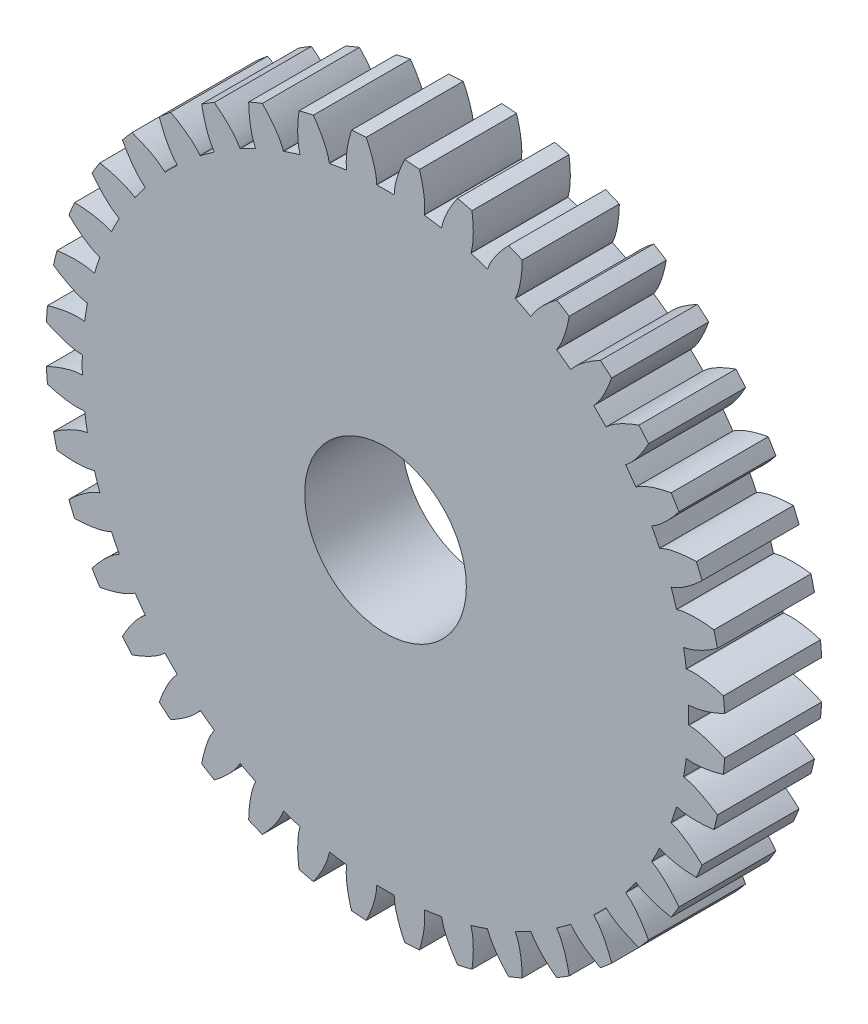
SolidWorks part; units mm, degrees
ref_plane "前视基准面" through (0, 0, 0) normal (0, 0, 1) x (1, 0, 0)
ref_plane "上视基准面" through (0, 0, 0) normal (0, 1, 0) x (1, 0, 0)
ref_plane "右视基准面" through (0, 0, 0) normal (1, 0, 0) x (0, 0, -1)
other "Configuration Table"
sketch "草图1" plane through (0, 0, 0) normal (0, 0, 1) x (1, 0, 0)
  line L0 (0, 0) -> (4, 0) construction
  line L1 (0, 0) -> (3.9969, 0.157) construction
  line L2 (0, 0) -> (3.7572, 0.1081)
  line L3 (3.9969, 0.157) -> (3.9969, -0.157) construction
  line L4 (0, 0) -> (3.7572, -0.1081)
  circle A0 centre (0, 0) radius 4.2
  circle A1 centre (0, 0) radius 4 construction
  circle A2 centre (0, 0) radius 3.75
  circle A3 centre (0, 0) radius 3.7588 construction
  circle A4 centre (0, 0) radius 1
  spline S0 degree 4 poles (3.7572, 0.1081) (3.7859, 0.1089) (3.8656, 0.1171) (4.0142, 0.1566) (4.244, 0.2529) (4.5194, 0.4228) (4.8383, 0.6887) (5.1613, 1.0532) (5.4549, 1.5001) (5.7635, 2.151) (5.9615, 2.8455) (6.0613, 3.5884) (6.0582, 4.4803) (5.9407, 5.366) (5.6554, 6.3645) (5.1709, 7.4112) (4.5413, 8.377) (3.7872, 9.2487) (2.9285, 10.0168) (1.983, 10.6749) (0.9682, 11.219) (0.0323, 11.5933) (-0.7245, 11.8205) (-1.2852, 11.952) (-1.6352, 12.022) (-1.9233, 12.071) (-2.1979, 12.1123) (-2.5004, 12.1475) (-2.7337, 12.1714) (-3.0025, 12.1902) (-3.2739, 12.2053) (-3.546, 12.2135) (-4.0234, 12.217) (-4.4129, 12.1964) (-4.8168, 12.1721) (-5.0123, 12.1473) (-5.1429, 12.1347) knots 0 0 0 0 0 0.005604 0.015718 0.02996 0.048734 0.068727 0.096889 0.125051 0.153212 0.209535 0.237696 0.271429 0.327752 0.384075 0.440398 0.496721 0.553044 0.609367 0.66569 0.722013 0.778336 0.806497 0.820578 0.834659 0.84874 0.86282 0.876901 0.890982 0.900036 0.909091 0.931818 0.954545 0.977273 1 1 1 1 1 construction
  spline S1 degree 4 poles (3.7572, 0.1081) (3.7859, 0.1089) (3.8656, 0.1171) (4.0142, 0.1566) (4.244, 0.2529) (4.5194, 0.4228) (4.8383, 0.6887) (5.1613, 1.0532) (5.4549, 1.5001) (5.7635, 2.151) (5.9615, 2.8455) (6.0613, 3.5884) (6.0582, 4.4803) (5.9407, 5.366) (5.6554, 6.3645) (5.1709, 7.4112) (4.5413, 8.377) (3.7872, 9.2487) (2.9285, 10.0168) (1.983, 10.6749) (0.9682, 11.219) (0.0323, 11.5933) (-0.7245, 11.8205) (-1.2852, 11.952) (-1.6352, 12.022) (-1.9233, 12.071) (-2.1979, 12.1123) (-2.5004, 12.1475) (-2.7337, 12.1714) (-3.0025, 12.1902) (-3.1616, 12.199) (-3.2457, 12.2029) (-3.2877, 12.2045) knots 0 0 0 0 0 0.005604 0.015718 0.02996 0.048734 0.068727 0.096889 0.125051 0.153212 0.209535 0.237696 0.271429 0.327752 0.384075 0.440398 0.496721 0.553044 0.609367 0.66569 0.722013 0.778336 0.806497 0.820578 0.834659 0.84874 0.86282 0.876901 0.890982 0.900036 0.909091 0.909091 0.909091 0.909091 0.909091
  spline S2 degree 4 poles (3.7572, -0.1081) (3.7859, -0.1089) (3.8656, -0.1171) (4.0142, -0.1566) (4.244, -0.2529) (4.5194, -0.4228) (4.8383, -0.6887) (5.1613, -1.0532) (5.4549, -1.5001) (5.7635, -2.151) (5.9615, -2.8455) (6.0613, -3.5884) (6.0582, -4.4803) (5.9407, -5.366) (5.6554, -6.3645) (5.1709, -7.4112) (4.5413, -8.377) (3.7872, -9.2487) (2.9285, -10.0168) (1.983, -10.6749) (0.9682, -11.219) (0.0323, -11.5933) (-0.7245, -11.8205) (-1.2852, -11.952) (-1.6352, -12.022) (-1.9233, -12.071) (-2.1979, -12.1123) (-2.5004, -12.1475) (-2.7337, -12.1714) (-3.0025, -12.1902) (-3.2739, -12.2053) (-3.546, -12.2135) (-4.0234, -12.217) (-4.4129, -12.1964) (-4.8168, -12.1721) (-5.0123, -12.1473) (-5.1429, -12.1347) knots 0 0 0 0 0 0.005604 0.015718 0.02996 0.048734 0.068727 0.096889 0.125051 0.153212 0.209535 0.237696 0.271429 0.327752 0.384075 0.440398 0.496721 0.553044 0.609367 0.66569 0.722013 0.778336 0.806497 0.820578 0.834659 0.84874 0.86282 0.876901 0.890982 0.900036 0.909091 0.931818 0.954545 0.977273 1 1 1 1 1 construction
  spline S3 degree 4 poles (3.7572, -0.1081) (3.7859, -0.1089) (3.8656, -0.1171) (4.0142, -0.1566) (4.244, -0.2529) (4.5194, -0.4228) (4.8383, -0.6887) (5.1613, -1.0532) (5.4549, -1.5001) (5.7635, -2.151) (5.9615, -2.8455) (6.0613, -3.5884) (6.0582, -4.4803) (5.9407, -5.366) (5.6554, -6.3645) (5.1709, -7.4112) (4.5413, -8.377) (3.7872, -9.2487) (2.9285, -10.0168) (1.983, -10.6749) (0.9682, -11.219) (0.0323, -11.5933) (-0.7245, -11.8205) (-1.2852, -11.952) (-1.6352, -12.022) (-1.9233, -12.071) (-2.1979, -12.1123) (-2.5004, -12.1475) (-2.7337, -12.1714) (-3.0025, -12.1902) (-3.1616, -12.199) (-3.2457, -12.2029) (-3.2877, -12.2045) knots 0 0 0 0 0 0.005604 0.015718 0.02996 0.048734 0.068727 0.096889 0.125051 0.153212 0.209535 0.237696 0.271429 0.327752 0.384075 0.440398 0.496721 0.553044 0.609367 0.66569 0.722013 0.778336 0.806497 0.820578 0.834659 0.84874 0.86282 0.876901 0.890982 0.900036 0.909091 0.909091 0.909091 0.909091 0.909091
  point P15 (3.9969, 0)
  dimension "齿顶圆直径" = 8.4
  dimension "分度圆直径" = 8
  dimension "齿根圆直径" = 7.5
  dimension "基圆直径" = 7.5175
  dimension "内孔直径" = 2
  dimension "渐近线镜像线夹角" = 2.25
extrude "凸台-拉伸1" add sketch "草图1" along normal blind 1.2 contours A0 | A4
extrude "切除-拉伸1" cut sketch "草图1<3>" along normal through all contours A2 S3 A0 S1 region at (4.0059, 0, 0)
sketch "草图1<3>" plane through (0, 0, 0) normal (0, 0, 1) x (1, 0, 0) same geometry as "草图1"
pattern_circular "阵列(圆周)1" count 40 every 9 about axis through (0, 0, 1.2) along (0, 0, 1) of "切除-拉伸1"
equation "\"m\"= 0.2'模数"
equation "\"z\" = 40'齿数"
equation "\"a\"= 20度'压力角"
equation "\"d\"= \"m\" * \"z\"'分度圆直径"
equation "\"da\"= ( \"z\" + 2 ) * \"m\"'齿顶圆直径"
equation "\"df\"= ( \"z\" - 2.5 ) * \"m\"'齿根圆直径"
equation "\"s\"= 0.5 * PI * \"m\"'分度圆齿厚"
equation "\"r\"= 0.38 * \"m\"'齿根圆角"
equation "\"B\"= 0.3 * \"d\"'齿厚"
equation "\"db\"= \"m\" * \"z\" * cos ( \"a\" )'基圆直径"
equation "\"rb\"= \"db\" / 2'基圆半径"
equation "\"齿顶圆直径@草图1\"= \"da\""
equation "\"分度圆直径@草图1\"= \"d\""
equation "\"齿根圆直径@草图1\"= \"df\""
equation "\"基圆直径@草图1\"= \"db\""
equation "\"渐近线镜像线夹角@草图1\"= 360 / 4 / \"z\""
equation "\"h\"= 1.2'齿轮厚度"
equation "\"ir\"= 2'内孔直径"
equation "\"内孔直径@草图1\"= \"ir\""
equation "\"齿轮厚@凸台-拉伸1\"= \"h\""
equation "\"齿轮夹角@阵列(圆周)1\"= 360 / \"z\""
equation "\"齿数@阵列(圆周)1\"= \"z\""
